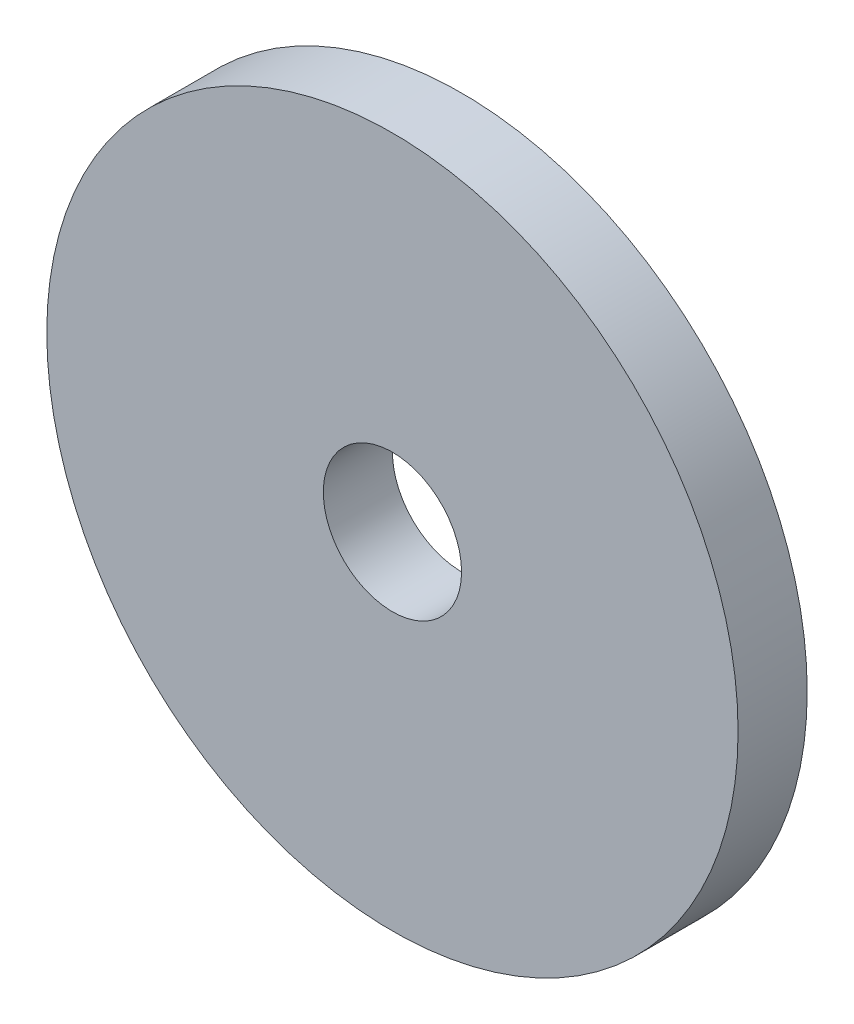
SolidWorks part; units mm, degrees
material "Сталь ШХ15 ГОСТ 801-78"
ref_plane "Plane1" through (0, 0, 0) normal (0, 0, 1) x (1, 0, 0)
ref_plane "Plane2" through (0, 0, 0) normal (0, 1, 0) x (1, 0, 0)
ref_plane "Plane3" through (0, 0, 0) normal (1, 0, 0) x (0, 0, -1)
sketch "Эскиз1" plane through (0, 0, 0) normal (0, 0, 1) x (1, 0, 0)
  circle A0 centre (0, 0) radius 10
  circle A1 centre (0, 0) radius 2
  dimension "D1" = 20
  dimension "D2" = 4
extrude "Бобышка-Вытянуть1" add sketch "Эскиз1" along normal blind 2 contours A1 | A0 region at (0, 0, 0)
